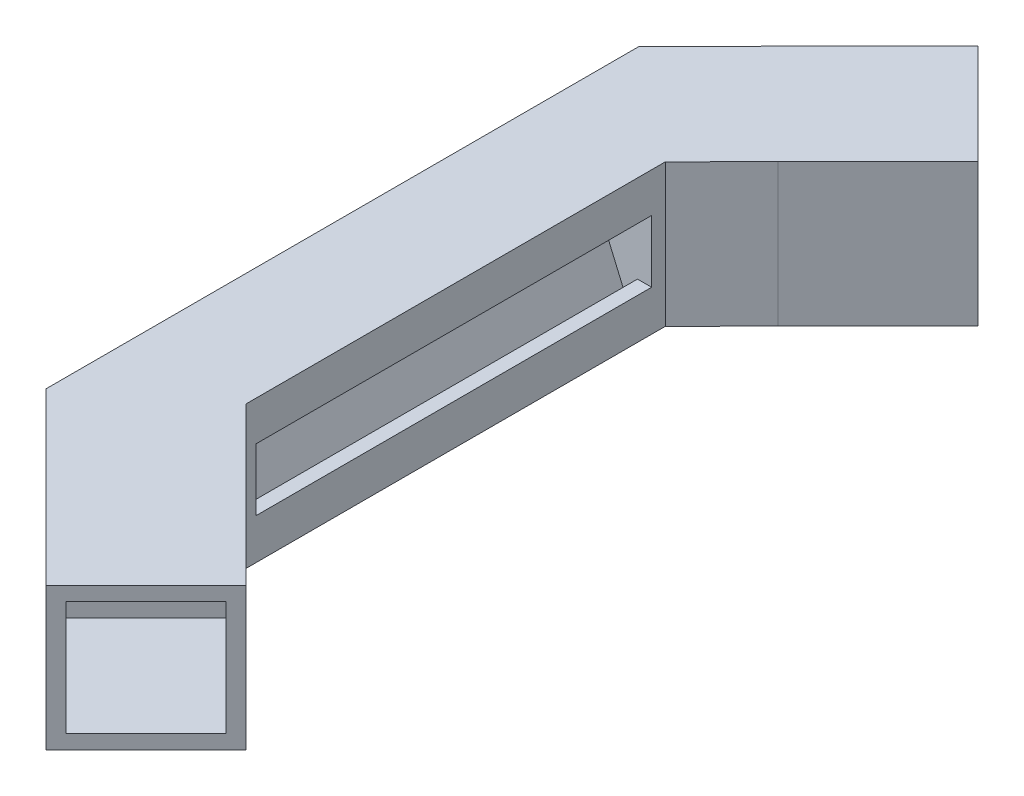
SolidWorks part; units mm, degrees
ref_plane "정면도" through (0, 0, 0) normal (0, 0, 1) x (1, 0, 0)
ref_plane "평면도" through (0, 0, 0) normal (0, 1, 0) x (1, 0, 0)
ref_plane "우측면도" through (0, 0, 0) normal (1, 0, 0) x (0, 0, -1)
sketch "스케치1" plane through (0, 0, 0) normal (0, 1, 0) x (1, 0, 0)
  line L0 (-24.8751, -66.2947) -> (-42.5528, -48.617) construction
  line L1 (-39.0173, -80.4368) -> (-56.695, -62.7592) construction
  line L2 (-25.0185, 66.8739) -> (-42.6942, 49.1981) construction
  line L3 (-39.1606, 81.016) -> (-56.8364, 63.3403) construction
  line L4 (-56.695, -62.7592) -> (-119.6778, 0.2237) construction
  line L5 (-42.5528, -48.617) -> (-91.3897, 0.2198) construction
  line L6 (-42.6942, 49.1981) -> (-91.3897, 0.2198) construction
  line L7 (-56.8364, 63.3403) -> (-119.6778, 0.2237) construction
  line L8 (-105.8732, 0.2198) -> (307.9107, 0.2198) construction
  line L9 (-40.7851, -82.2046) -> (-58.4627, -64.5269)
  line L10 (-58.4627, -64.5269) -> (-123.2095, 0.2198) construction
  line L11 (-58.6061, 65.1061) -> (-123.2095, 0.2198) construction
  line L12 (-40.9284, 82.7838) -> (-58.6061, 65.1061)
  line L13 (-23.1074, -64.5269) -> (-40.7851, -46.8493)
  line L14 (-40.7851, -46.8493) -> (-87.8593, 0.2249) construction
  line L15 (-40.9239, 47.4329) -> (-87.8593, 0.2249) construction
  line L16 (-23.2507, 65.1061) -> (-40.9239, 47.4329)
  line L17 (-105.8732, 0.2198) -> (-306.1732, 0.2198) construction
  line L18 (-40.7851, -82.2046) -> (-23.1074, -64.5269)
  line L19 (-40.9284, 82.7838) -> (-23.2507, 65.1061)
  line L20 (-70.8732, -52.1164) -> (-70.8732, 52.7852)
  line L21 (-50.8732, -36.7611) -> (-50.8732, 37.4258)
  line L22 (-58.4627, -64.5269) -> (-70.8732, -52.1164)
  line L23 (-40.7851, -46.8493) -> (-50.8732, -36.7611)
  line L24 (-40.9239, 47.4329) -> (-50.8732, 37.4258)
  line L25 (-70.8732, 52.7852) -> (-58.6061, 65.1061)
  dimension "D1" = 25
  dimension "D2" = 20
  dimension "D3" = 55
extrude "보스-돌출1" add sketch "스케치1" along normal blind 2.5 contours L9 L22 L20 L25 L12 L19 L16 L24 L21 L23 L13 L18
sketch "스케치2" plane through (0, 2.5, 0) normal (0, 1, 0) x (1, 0, 0)
  line L0 (-25.0185, 66.8739) -> (-42.6942, 49.1981) construction
  line L1 (-39.1606, 81.016) -> (-56.8364, 63.3403) construction
  line L2 (-24.8751, -66.2947) -> (-42.5528, -48.617) construction
  line L3 (-39.0173, -80.4368) -> (-56.695, -62.7592) construction
  line L4 (-25.0185, 66.8739) -> (-42.6942, 49.1981)
  line L5 (-39.1606, 81.016) -> (-56.8364, 63.3403)
  line L6 (-24.8751, -66.2947) -> (-42.5528, -48.617)
  line L7 (-39.0173, -80.4368) -> (-56.695, -62.7592)
  line L8 (-56.695, -62.7592) -> (-42.5528, -48.617)
  line L9 (-56.8364, 63.3403) -> (-42.6942, 49.1981)
  line L10 (-40.7851, -82.2046) -> (-23.1074, -64.5269)
  line L11 (-23.1074, -64.5269) -> (-50.8732, -36.7611)
  line L12 (-50.8732, -36.7611) -> (-50.8732, 37.4258)
  line L13 (-50.8732, 37.4258) -> (-40.9239, 47.4329)
  line L14 (-40.9239, 47.4329) -> (-23.2507, 65.1061)
  line L15 (-23.2507, 65.1061) -> (-40.9284, 82.7838)
  line L16 (-40.9284, 82.7838) -> (-58.6061, 65.1061)
  line L17 (-58.6061, 65.1061) -> (-70.8732, 52.7852)
  line L18 (-70.8732, 52.7852) -> (-70.8732, -52.1164)
  line L19 (-70.8732, -52.1164) -> (-40.7851, -82.2046)
  line L20 (-40.7851, -82.2046) -> (-39.0173, -80.4368)
  line L21 (-23.1074, -64.5269) -> (-50.8732, -36.7611)
  line L22 (-50.8732, -36.7611) -> (-50.8732, 37.4258)
  line L23 (-50.8732, 37.4258) -> (-40.9239, 47.4329)
  line L24 (-40.9239, 47.4329) -> (-23.2507, 65.1061)
  line L25 (-23.2507, 65.1061) -> (-25.0185, 66.8739)
  line L26 (-40.9284, 82.7838) -> (-58.6061, 65.1061)
  line L27 (-58.6061, 65.1061) -> (-70.8732, 52.7852)
  line L28 (-70.8732, 52.7852) -> (-70.8732, -52.1164)
  line L29 (-70.8732, -52.1164) -> (-40.7851, -82.2046)
  line L30 (-39.1606, 81.016) -> (-40.9284, 82.7838)
  line L31 (-24.8751, -66.2947) -> (-23.1074, -64.5269)
  dimension "D1" = 0
extrude "보스-돌출2" add sketch "스케치2" along normal blind 20.2
sketch "스케치3" plane through (0, 22.7, 0) normal (0, 1, 0) x (1, 0, 0)
  line L10 (-40.7851, -82.2046) -> (-23.1074, -64.5269)
  line L11 (-70.8732, -52.1164) -> (-40.7851, -82.2046)
  line L12 (-70.8732, 52.7852) -> (-70.8732, -52.1164)
  line L13 (-58.6061, 65.1061) -> (-70.8732, 52.7852)
  line L14 (-40.9284, 82.7838) -> (-58.6061, 65.1061)
  line L15 (-23.2507, 65.1061) -> (-40.9284, 82.7838)
  line L16 (-40.9239, 47.4329) -> (-23.2507, 65.1061)
  line L17 (-50.8732, 37.4258) -> (-40.9239, 47.4329)
  line L18 (-50.8732, -36.7611) -> (-50.8732, 37.4258)
  line L19 (-23.1074, -64.5269) -> (-50.8732, -36.7611)
  line L20 (-40.7851, -82.2046) -> (-23.1074, -64.5269)
  line L21 (-70.8732, -52.1164) -> (-40.7851, -82.2046)
  line L22 (-70.8732, 52.7852) -> (-70.8732, -52.1164)
  line L23 (-58.6061, 65.1061) -> (-70.8732, 52.7852)
  line L24 (-40.9284, 82.7838) -> (-58.6061, 65.1061)
  line L25 (-23.2507, 65.1061) -> (-40.9284, 82.7838)
  line L26 (-40.9239, 47.4329) -> (-23.2507, 65.1061)
  line L27 (-50.8732, 37.4258) -> (-40.9239, 47.4329)
  line L28 (-50.8732, -36.7611) -> (-50.8732, 37.4258)
  line L29 (-23.1074, -64.5269) -> (-50.8732, -36.7611)
  dimension "D1" = 0
extrude "보스-돌출3" add sketch "스케치3" along normal blind 2.5
sketch "스케치4" plane through (0, 0, 0) normal (0, 0, 1) x (1, 0, 0)
  line L5 (-50.8732, 25.2) -> (-50.8732, 0) construction
  line L6 (-50.8732, 18.2) -> (-50.8732, 16.5078)
  line L7 (-70.8732, 18.2) -> (-68.3732, 18.2)
  line L8 (-50.8732, 8.8922) -> (-50.8732, 7.2)
  line L9 (-68.3732, 7.2) -> (-70.8732, 7.2)
  line L13 (-68.3732, 18.2) -> (-68.3732, 23.2)
  line L16 (-68.3732, 7.2) -> (-68.3732, 2.2)
  line L19 (-70.8732, 18.2) -> (-70.8732, 7.2)
  line L20 (-50.8732, 16.5078) -> (-50.8732, 8.8922)
  line L21 (-68.3732, 23.2) -> (-66.8732, 23.2)
  line L22 (-66.8732, 23.2) -> (-62.3732, 12.7)
  line L23 (-70.8732, 12.7) -> (-50.8732, 12.7) construction
  line L24 (-60.8732, 25.2) -> (-60.8732, 0) construction
  line L25 (-62.3732, 12.7) -> (-66.8732, 2.2)
  line L26 (-66.8732, 2.2) -> (-68.3732, 2.2)
  line L27 (-53.3732, 7.2) -> (-50.8732, 7.2)
  line L28 (-53.3732, 7.2) -> (-53.3732, 2.2)
  line L29 (-54.8732, 2.2) -> (-53.3732, 2.2)
  line L30 (-59.3732, 12.7) -> (-54.8732, 2.2)
  line L31 (-54.8732, 23.2) -> (-59.3732, 12.7)
  line L32 (-53.3732, 23.2) -> (-54.8732, 23.2)
  line L33 (-53.3732, 18.2) -> (-53.3732, 23.2)
  line L34 (-50.8732, 18.2) -> (-53.3732, 18.2)
  dimension "D1" = 2.5
  dimension "D2" = 2.5
  dimension "D4" = 5
  dimension "D5" = 5
  dimension "D7" = 1.5
  dimension "D8" = 1.5
  dimension "D9" = 1.5
extrude "컷-돌출1" cut sketch "스케치4" against normal blind 35 and the other way blind 35 contours L22 L25 L26 L16 L9 L19 L7 L13 L21 | L33 L32 L31 L30 L29 L28 L27 L8 L20 L6 L34
